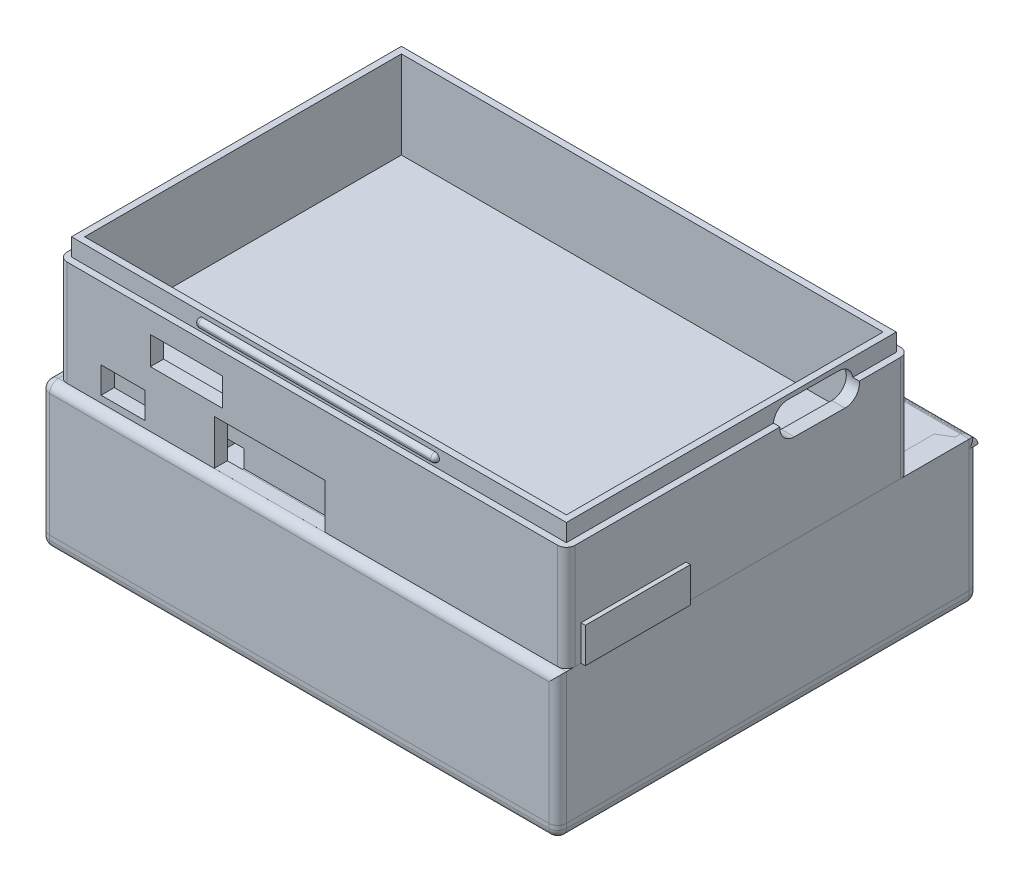
SolidWorks part; units mm, degrees
ref_plane "Front Plane" through (0, 0, 0) normal (0, 0, 1) x (1, 0, 0)
ref_plane "Top Plane" through (0, 0, 0) normal (0, 1, 0) x (1, 0, 0)
ref_plane "Right Plane" through (0, 0, 0) normal (1, 0, 0) x (0, 0, -1)
ref_plane "Plane1" through (0, 15, 0) normal (0, 1, 0) x (1, 0, 0)
sketch "Sketch2" plane through (0, 0, 0) normal (0, 1, 0) x (1, 0, 0)
  line L1 (-27, -21.5) -> (27, -21.5)
  line L2 (-27, -21.5) -> (-27, 21.5)
  line L3 (-27, 21.5) -> (27, 21.5)
  line L4 (27, -21.5) -> (27, 21.5)
  line L5 (-27, -21.5) -> (27, 21.5) construction
  line L6 (-27, 21.5) -> (27, -21.5) construction
  point P0 (0, 0)
  dimension "D1" = 54
  dimension "D2" = 43
extrude "Boss-Extrude1-Battery" add sketch "Sketch2" along normal blind 14
sketch "Sketch4" plane through (0, 15, 0) normal (0, 1, 0) x (1, 0, 0)
  line L1 (-27, -21.3333) -> (28, -21.3333)
  line L2 (-27, -21.3333) -> (-27, 14.6667)
  line L3 (-27, 14.6667) -> (28, 14.6667)
  line L4 (28, -21.3333) -> (28, 14.6667)
  line L5 (-27, -21.3333) -> (28, 14.6667) construction
  line L6 (-27, 14.6667) -> (28, -21.3333) construction
  point P0 (0, 0)
  dimension "D1" = 55
  dimension "D2" = 36
extrude "Boss-Extrude2-Circuit" add sketch "Sketch4" along normal blind 14
sketch "Sketch8" plane through (0, 0, 21.3333) normal (0, 0, 1) x (1, 0, 0)
  line L1 (28, 15) -> (-9, 15)
  line L2 (28, 15) -> (28, 17)
  line L3 (28, 17) -> (-9, 17)
  line L4 (-9, 15) -> (-9, 17)
  line L6 (-9, 17) -> (-9, 15)
  line L7 (-9, 15) -> (-27, 15)
  line L8 (-27, 17) -> (-27, 15)
  line L9 (-27, 17) -> (-17, 17)
  line L10 (-27, 17) -> (-27, 15)
  line L11 (-27, 15) -> (-17, 15)
  line L12 (-17, 17) -> (-17, 15)
  line L13 (-17, 17) -> (-9, 17)
  line L14 (-17, 17) -> (-17, 15)
  line L15 (-17, 15) -> (-9, 15)
  line L16 (-9, 17) -> (-9, 15)
  dimension "D1" = 2
  dimension "D2" = 37
  dimension "D4" = 10
sketch "Sketch11" plane through (28, 0, 0) normal (1, 0, 0) x (0, 0, -1)
  line L0 (14.6667, 29) -> (14.6667, 15) construction
  line L1 (-21.3333, 15) -> (-12.3333, 15)
  line L2 (-21.3333, 15) -> (-21.3333, 17)
  line L3 (-21.3333, 17) -> (-12.3333, 17)
  line L4 (-12.3333, 15) -> (-12.3333, 17)
  line L5 (-12.3333, 15) -> (14.6667, 15)
  line L6 (-12.3333, 15) -> (-12.3333, 17)
  line L7 (-12.3333, 17) -> (14.6667, 17)
  line L8 (14.6667, 15) -> (14.6667, 17)
  line M3 (-21.3333, 15) -> (14.6667, 15)
  line M4 (14.6667, 15) -> (14.6667, 29)
  dimension "D1" = 9
  dimension "D2" = 2
extrude "Cut-Extrude2-CutPins" cut sketch "Sketch11" against normal blind 55 contours L7 L4 M3 M4 region at (28, 16, -1.1667)
sketch "Sketch12" plane through (28, 0, 0) normal (1, 0, 0) x (0, 0, -1)
  line L1 (-21.3333, 15) -> (-9.3333, 15)
  line L2 (-21.3333, 15) -> (-21.3333, 19)
  line L3 (-21.3333, 19) -> (-9.3333, 19)
  line L4 (-9.3333, 15) -> (-9.3333, 19)
  dimension "D1" = 4
  dimension "D2" = 12
extrude "Boss-Extrude1-BatteryCon" add sketch "Sketch12" along normal blind 2
extrude "Cut-Extrude3-SwitchConnGap" cut sketch "Sketch8" against normal blind 10 contours L13 L12 L7 L4 region at (-13, 16, 21.3333)
sketch "Sketch13" plane through (0, 0, 0) normal (0, 1, 0) x (1, 0, 0)
  line L1 (-27, 21.5) -> (27, 21.5)
  line L2 (-27, 21.5) -> (-27, -21.5)
  line L3 (-27, -21.5) -> (27, -21.5)
  line L4 (27, 21.5) -> (27, -21.5)
  line L8 (-29.5, 24) -> (-29.5, -24)
  line L9 (-29.5, -24) -> (29.5, -24)
  line L10 (29.5, 24) -> (29.5, -24)
  line L11 (-29.5, 24) -> (29.5, 24)
  dimension "D1" = 2.5
extrude "Boss-Extrude4" add sketch "Sketch13" along normal blind 15 separate body
ref_plane "Plane2" through (0, 14, 0) normal (0, 1, 0) x (1, 0, 0)
sketch "Sketch14" plane through (0, 14, 0) normal (0, 1, 0) x (1, 0, 0)
  line L0 (-25.5, 13.1667) -> (-25.5, -20)
  line L1 (-29.5, 24) -> (29.5, 24)
  line L2 (-29.5, 24) -> (-29.5, -24)
  line L3 (-29.5, -24) -> (29.5, -24)
  line L4 (29.5, 24) -> (29.5, -24)
  line L5 (-29.5, 24) -> (29.5, 24)
  line L6 (-29.5, 24) -> (-29.5, 14.6667)
  line L7 (-29.5, 14.6667) -> (29.5, 14.6667)
  line L8 (29.5, 24) -> (29.5, 14.6667)
  line L9 (-27, 14.6667) -> (27, 14.6667)
  line L10 (-27, 14.6667) -> (-27, -21.5)
  line L11 (-27, -21.5) -> (27, -21.5)
  line L12 (27, 14.6667) -> (27, -21.5)
  line L13 (-25.5, -20) -> (25.5, -20)
  line L14 (25.5, 13.1667) -> (25.5, -20)
  line L15 (-25.5, 13.1667) -> (25.5, 13.1667)
  line L17 (-27, -12.3333) -> (-17, -12.3333)
  line L18 (-27, -12.3333) -> (-27, -21.5)
  line L19 (-27, -21.5) -> (-17, -21.5)
  line L20 (-17, -12.3333) -> (-17, -21.5)
  line L21 (-8.9929, -12.3333) -> (27, -12.3333)
  line L22 (-8.9929, -12.3333) -> (-8.9929, -21.5)
  line L23 (-8.9929, -21.5) -> (27, -21.5)
  line L24 (27, -12.3333) -> (27, -21.5)
  line L25 (27, -12.3333) -> (25.5, -12.3333)
  line L26 (27, -12.3333) -> (27, -9.3333)
  line L27 (27, -9.3333) -> (25.5, -9.3333)
  line L28 (25.5, -12.3333) -> (25.5, -9.3333)
  line L29 (27, -9.3333) -> (21.2621, -9.3333)
  line L30 (27, -9.3333) -> (27, -21.5)
  line L31 (27, -21.5) -> (21.2621, -21.5)
  line L32 (21.2621, -9.3333) -> (21.2621, -21.5)
  dimension "D2" = 5.7379
  dimension "D1" = 1.5
extrude "Boss-Extrude6" add sketch "Sketch14" along normal blind 3 separate body contours L27 L12 L7 L10 L17 L0 L15 L14 region at (-26.1037, 14, -0.4167)
extrude "Boss-Extrude7" add sketch "Sketch14<6>" along normal blind 1 separate body contours L20 L13 L0 L17 L10 L11 | L32 L13 L22 L11 region at (-25.6357, 14, 16.1667) region at (6.1346, 14, 20.75)
sketch "Sketch14<6>" plane through (0, 14, 0) normal (0, 1, 0) x (1, 0, 0) same geometry as "Sketch14"
extrude "Boss-Extrude9" add sketch "Sketch14<7>" along normal blind 1 separate body contours L2 L7 L4 L1 region at (0, 14, -19.3333)
sketch "Sketch14<7>" plane through (0, 14, 0) normal (0, 1, 0) x (1, 0, 0) same geometry as "Sketch14"
sketch "Sketch15" plane through (0, 15, 0) normal (0, 1, 0) x (1, 0, 0)
  line L0 (-28.5, 16.1667) -> (-28.5, -23)
  line L1 (-27, 14.6667) -> (28, 14.6667)
  line L2 (-27, 14.6667) -> (-27, -21.5)
  line L3 (-27, -21.5) -> (28, -21.5)
  line L4 (28, 14.6667) -> (28, -21.5)
  line L5 (-28.5, -23) -> (29.5, -23)
  line L6 (29.5, 16.1667) -> (29.5, -23)
  line L7 (-28.5, 16.1667) -> (29.5, 16.1667)
  dimension "D1" = 1.5
extrude "Boss-Extrude10" add sketch "Sketch15" along normal blind 14 separate body
sketch "Sketch16" plane through (0, 29, 0) normal (0, 1, 0) x (1, 0, 0)
  line L0 (-27.75, 15.4167) -> (-27.75, -22.25)
  line L1 (-28.5, 16.1667) -> (29.5, 16.1667)
  line L2 (-28.5, 16.1667) -> (-28.5, -23)
  line L3 (-28.5, -23) -> (29.5, -23)
  line L4 (29.5, 16.1667) -> (29.5, -23)
  line L5 (-27.75, -22.25) -> (28.75, -22.25)
  line L6 (28.75, 15.4167) -> (28.75, -22.25)
  line L7 (-27.75, 15.4167) -> (28.75, 15.4167)
  dimension "D1" = 0.75
extrude "Cut-Extrude-LidCut" cut sketch "Sketch16" against normal blind 2
ref_plane "Plane3" through (0, 0, 3.4167) normal (0, 0, -1) x (-1, 0, 0)
sketch "Sketch17" plane through (0, 0, 22.25) normal (0, 0, 1) x (1, 0, 0)
  line L0 (-12.75, 28) -> (13.75, 28) construction
  line L1 (-12.75, 28.5) -> (13.75, 28.5)
  line L2 (-12.75, 27.5) -> (13.75, 27.5)
  line L3 (-27.75, 29) -> (28.75, 29) construction
  line L4 (-28.5, 27) -> (29.5, 27) construction
  line L5 (28.75, 27) -> (28.75, 29) construction
  line L6 (-27.75, 27) -> (-27.75, 29) construction
  arc A0 (-12.75, 28.5) -> (-12.75, 27.5) centre (-12.75, 28) ccw
  arc A1 (13.75, 27.5) -> (13.75, 28.5) centre (13.75, 28) ccw
  point P2 (0.5, 28)
  dimension "D1" = 0.5
  dimension "D2" = 0.5
  dimension "D3" = 15
  dimension "D4" = 15
extrude "Boss-Extrude11" add sketch "Sketch17" along normal blind 0.5
fillet "Fillet5" radius 0.5 4 edges at (14.25, 28, 22.75) (-13.25, 28, 22.75) (0.5, 27.5, 22.75) (0.5, 28.5, 22.75)
mirror "Mirror1" about plane through (0, 0, 3.4167) normal (0, 0, -1) of "Fillet5", "Boss-Extrude11"
sketch "Sketch18" plane through (0, 0, 0) normal (0, -1, 0) x (1, 0, 0)
  line L0 (29.5, 24) -> (29.5, -24) construction
  line L1 (-29.5, 24) -> (29.5, 24)
  line L2 (-29.5, 24) -> (-29.5, -24)
  line L3 (-29.5, -24) -> (29.5, -24)
  line L4 (29.5, 24) -> (29.5, -24)
  line L5 (29.5, -24) -> (-29.5, -24) construction
extrude "Boss-Extrude13" add sketch "Sketch18" along normal blind 1.5 separate body
fillet "Fillet6" radius 1 7 edges at (29.5, 7.5, -24) (29.5, 7.5, 24) (-29.5, 7.5, 24) (-29.5, 7.5, -24) (0, 15, -24) (0, 15, 24) (-29.5, 15, 0)
fillet "Fillet7" radius 1 3 edges at (29.5, 15, -19.3333) (0, 15, -24) (-29.5, 15, -19.3333)
fillet "Fillet8" radius 1 4 edges at (29.5, 21, 23) (29.5, 21, -16.1667) (-28.5, 21, 23) (-28.5, 21, -16.1667)
fillet "Fillet9" radius 1 8 edges at (-29.5, -0.75, -24) (0, -1.5, -24) (-29.5, -0.75, 24) (-29.5, -1.5, 0) (0, -1.5, 24) (29.5, -0.75, 24) (29.5, -1.5, 0) (29.5, -0.75, -24)
extrude "Cut-Extrude1" cut sketch "Sketch2<3>" along normal blind 14
sketch "Sketch2<3>" plane through (0, 0, 0) normal (0, 1, 0) x (1, 0, 0) same geometry as "Sketch2"
sketch "Sketch19" plane through (0, 29, 0) normal (0, 1, 0) x (1, 0, 0)
  line L1 (-27, 14.6667) -> (28, 14.6667)
  line L2 (-27, 14.6667) -> (-27, -21.5)
  line L3 (-27, -21.5) -> (28, -21.5)
  line L4 (28, 14.6667) -> (28, -21.5)
extrude "Cut-Extrude5" cut sketch "Sketch19" against normal blind 10
sketch "Sketch20" plane through (0, 0, 21.3333) normal (0, 0, 1) x (1, 0, 0)
  line L0 (-23.6176, 15.7749) -> (-23.6176, 18.7748)
  line L5 (-23.6176, 18.7748) -> (-18.6235, 18.7748)
  line L6 (-18.6235, 15.7749) -> (-18.6235, 18.7748)
  line L7 (-23.6176, 15.7749) -> (-18.6235, 15.7749)
  line L8 (-27.5, 15) -> (28.5, 15) construction
  line L9 (-9.8306, 15.8711) -> (1.0694, 15.8711)
  line L13 (-10.7006, 20.1409) -> (1.9394, 20.1409)
  line L14 (1.9394, 15.0011) -> (1.9394, 20.1409)
  line L15 (-10.7006, 15.0011) -> (1.9394, 15.0011)
  line L16 (-10.7006, 15.0011) -> (-10.7006, 20.1409)
  line L17 (-17.9916, 21.4104) -> (-17.9916, 24.5944)
  line L22 (-17.9916, 24.5944) -> (-9.7416, 24.5944)
  line L23 (-9.7416, 21.4104) -> (-9.7416, 24.5944)
  line L24 (-17.9916, 21.4104) -> (-9.7416, 21.4104)
  line L26 (-23.6176, 18.7748) -> (-18.6235, 18.7748)
  line L27 (-23.6176, 18.7748) -> (-23.6176, 15.7749)
  line L28 (-23.6176, 15.7749) -> (-18.6235, 15.7749)
  line L29 (-18.6235, 18.7748) -> (-18.6235, 15.7749)
  line L30 (-17.9916, 24.5944) -> (-9.7416, 24.5944)
  line L31 (-17.9916, 24.5944) -> (-17.9916, 21.4104)
  line L32 (-17.9916, 21.4104) -> (-9.7416, 21.4104)
  line L33 (-9.7416, 24.5944) -> (-9.7416, 21.4104)
  line L34 (-10.7006, 20.1409) -> (1.9394, 20.1409)
  line L35 (-10.7006, 20.1409) -> (-10.7006, 15.0011)
  line L36 (-10.7006, 15.0011) -> (1.9394, 15.0011)
  line L37 (1.9394, 20.1409) -> (1.9394, 15.0011)
  line L38 (-17.9916, 24.5944) -> (-9.7416, 24.5944)
  line L39 (-17.9916, 24.5944) -> (-17.9916, 21.4104)
  line L40 (-17.9916, 21.4104) -> (-9.7416, 21.4104)
  line L41 (-9.7416, 24.5944) -> (-9.7416, 21.4104)
  line L42 (-23.6176, 18.7748) -> (-18.6235, 18.7748)
  line L43 (-23.6176, 18.7748) -> (-23.6176, 15.7749)
  line L44 (-23.6176, 15.7749) -> (-18.6235, 15.7749)
  line L45 (-18.6235, 18.7748) -> (-18.6235, 15.7749)
  line L46 (-9.8306, 19.2709) -> (1.0694, 19.2709) construction
  line L47 (-9.8306, 15.8711) -> (-9.8306, 19.2709) construction
  line L48 (1.0694, 15.8711) -> (1.0694, 19.2709) construction
  line L49 (-10.7006, 20.1409) -> (1.9394, 20.1409)
  line L50 (-10.7006, 20.1409) -> (-10.7006, 15.0011)
  line L51 (-10.7006, 15.0011) -> (1.9394, 15.0011)
  line L52 (1.9394, 20.1409) -> (1.9394, 15.0011)
  line M5 (30, 19) -> (-27, 19)
  line M9 (-17, 17) -> (-9, 17)
  line M10 (-9, 17) -> (-9, 15)
  dimension "D2" = 0.8711
extrude "Cut-Extrude6" cut sketch "Sketch20" along normal blind 3 contours L0 L7 L6 L5 | L17 L24 L23 L22 | L16 L14 L13 M5 | L16 L15 L14 M9 M10 M5 | L16 L15 M10 M9 region at (-21.1206, 17.2748, 21.3333) region at (-4.3806, 19.5705, 21.3333) region at (-3.9862, 17.0726, 21.3333) region at (-9.8503, 16.0005, 21.3333) region at (-13.8666, 23.0024, 21.3333)
sketch "Sketch21" plane through (27, 0, 0) normal (1, 0, 0) x (0, 0, -1)
  line L0 (3.0378, 26.8535) -> (8.8175, 26.8031) construction
  line L1 (3.0521, 28.4996) -> (8.8319, 28.4492)
  line L2 (3.0234, 25.2074) -> (8.8032, 25.157)
  arc A0 (3.0521, 28.4996) -> (3.0234, 25.2074) centre (3.0378, 26.8535) ccw
  arc A1 (8.8032, 25.157) -> (8.8319, 28.4492) centre (8.8175, 26.8031) ccw
  point P4 (5.9276, 26.8283)
extrude "Cut-Extrude7" cut sketch "Sketch21" along normal blind 3
sketch "Sketch22" [suppressed] plane through (28.75, 0, 0) normal (1, 0, 0) x (0, 0, -1)
  line L0 (-22.25, 27) -> (1.3981, 27)
  line L1 (1.3981, 27) -> (1.3981, 29)
  line L2 (1.3981, 27) -> (10.4519, 27)
  line L3 (10.4519, 27) -> (15.4167, 27)
  line L5 (-22.25, 29) -> (15.4167, 29) construction
  dimension "D1" = 9.0537
  dimension "D2" = 4.9648
  dimension "D3" = 23.6481
  dimension "D4" = 2
